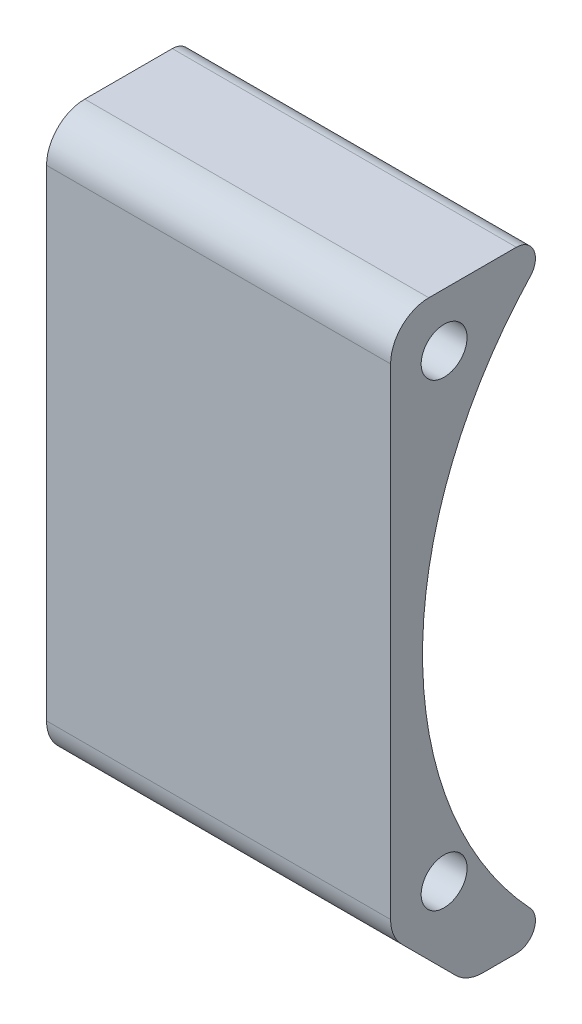
SolidWorks part; units mm, degrees
ref_plane "Front Plane" through (0, 0, 0) normal (0, 0, 1) x (1, 0, 0)
ref_plane "Top Plane" through (0, 0, 0) normal (0, 1, 0) x (1, 0, 0)
ref_plane "Right Plane" through (0, 0, 0) normal (1, 0, 0) x (0, 0, -1)
sketch "Sketch1" plane through (0, 0, 0) normal (1, 0, 0) x (0, 0, -1)
  line L0 (0, 0) -> (0, 50.8)
  line L1 (0, 50.8) -> (14.3998, 50.8)
  line L2 (0, 0) -> (14.3998, 0)
  arc A0 (14.3998, 50.8) -> (14.3998, 0) centre (35.9921, 25.4) ccw
  point P6 (39.1672, 25.4)
  point P8 (17.2454, 50.8)
  dimension "D1" = 50.8
  dimension "D2" = 66.675
extrude "Boss-Extrude1" add sketch "Sketch1" along normal blind 28.575
chamfer "Chamfer1" distance 6.35 angle 45 1 edges at (14.2875, 0, 0)
fillet "Fillet1" radius 3.175 3 edges at (14.2875, 6.35, 0) (14.2875, 0, -6.35) (14.2875, 50.8, 0)
fillet "Fillet2" radius 1.5875 2 edges at (14.2875, 50.8, -14.3998) (14.2875, 0, -14.3998)
sketch "Sketch2" plane through (28.575, 0, 0) normal (1, 0, 0) x (0, 0, -1)
  line L0 (10.4437, 50.8) -> (3.175, 50.8) construction
  line L1 (0, 47.625) -> (0, 7.6651) construction
  line L2 (0.9299, 5.4201) -> (5.4201, 0.9299) construction
  circle A0 centre (4.445, 46.355) radius 4.445 construction
  circle A1 centre (4.445, 8.1912) radius 4.445 construction
  point P0 (4.445, 46.355)
  point P2 (4.445, 8.1912)
  dimension "D1" = 8.89
hole_wizard "#8 Clearance Hole1" positions "Sketch2" profile "Sketch3" hole size "#8" standard "ANSI Inch" end condition through all
sketch "Sketch3" plane through (28.575, 46.355, -4.445) normal (0, 1, 0) x (0, 0, -1)
  line L0 (0, 0) -> (0, 28.575)
  line L1 (0, 28.575) -> (1.905, 28.575)
  line L2 (1.905, 28.575) -> (1.905, 0)
  line L5 (1.905, 0) -> (0, 0)
  line L11 (0, -6.35) -> (0, 107.95) construction
  dimension "Thru Hole Dia." = 3.81
  dimension "Thru Hole Depth" = 28.575
sketch "Sketch4" plane through (0, 0, 0) normal (-1, 0, 0) x (0, 0, 1)
  line L0 (-4.445, 49.53) -> (-11.9991, 49.53)
  line L1 (-4.445, 43.18) -> (-7.7917, 43.18)
  line L2 (-4.445, 11.3662) -> (-5.7524, 11.3662)
  line L3 (-4.445, 5.0162) -> (-9.6124, 5.0162)
  arc A0 (-4.445, 43.18) -> (-4.445, 49.53) centre (-4.445, 46.355) ccw
  arc A1 (-4.445, 5.0162) -> (-4.445, 11.3662) centre (-4.445, 8.1912) ccw
  arc A2 (-11.605, 2.6699) -> (-11.605, 48.1301) centre (-35.9921, 25.4) ccw construction
  arc A3 (-9.6124, 5.0162) -> (-5.7524, 11.3662) centre (-35.9921, 25.4) ccw
  arc A4 (-10.4437, 50.8) -> (-11.605, 48.1301) centre (-10.4437, 49.2125) ccw construction
  arc A5 (-11.9991, 49.53) -> (-11.605, 48.1301) centre (-10.4437, 49.2125) ccw
  arc A6 (-7.7917, 43.18) -> (-11.605, 48.1301) centre (-35.9921, 25.4) ccw
  dimension "D1" = 6.35
extrude "Cut-Extrude1" cut sketch "Sketch4" against normal blind 6.35
sketch "Sketch5" [suppressed] plane through (28.575, 0, 0) normal (1, 0, 0) x (0, 0, -1)
  line L0 (4.7625, 49.2125) -> (13.534, 49.2125)
  line L1 (4.7625, 42.8625) -> (10.2902, 42.8625)
  line L4 (4.7625, 11.4977) -> (8.8696, 11.4977)
  line L5 (4.7625, 5.1477) -> (11.6784, 5.1477)
  arc A0 (4.7625, 49.2125) -> (4.7625, 42.8625) centre (4.7625, 46.0375) ccw
  arc A1 (4.7625, 11.4977) -> (4.7625, 5.1477) centre (4.7625, 8.3227) ccw
  arc A2 (13.2807, 48.3523) -> (11.9465, 50.8) centre (11.9465, 49.2125) ccw construction
  arc A3 (13.2807, 48.3523) -> (13.2807, 2.4477) centre (48.8816, 25.4) ccw construction
  arc A4 (13.2807, 48.3523) -> (10.2902, 42.8625) centre (48.8816, 25.4) ccw
  arc A5 (13.2807, 48.3523) -> (13.534, 49.2125) centre (11.9465, 49.2125) ccw
  arc A6 (8.8696, 11.4977) -> (11.6784, 5.1477) centre (48.8816, 25.4) ccw
  circle A7 centre (4.7625, 8.3227) radius 1.905 construction
  dimension "D1" = 6.35
extrude "Cut-Extrude2" [suppressed] cut sketch "Sketch5" against normal blind 6.35
